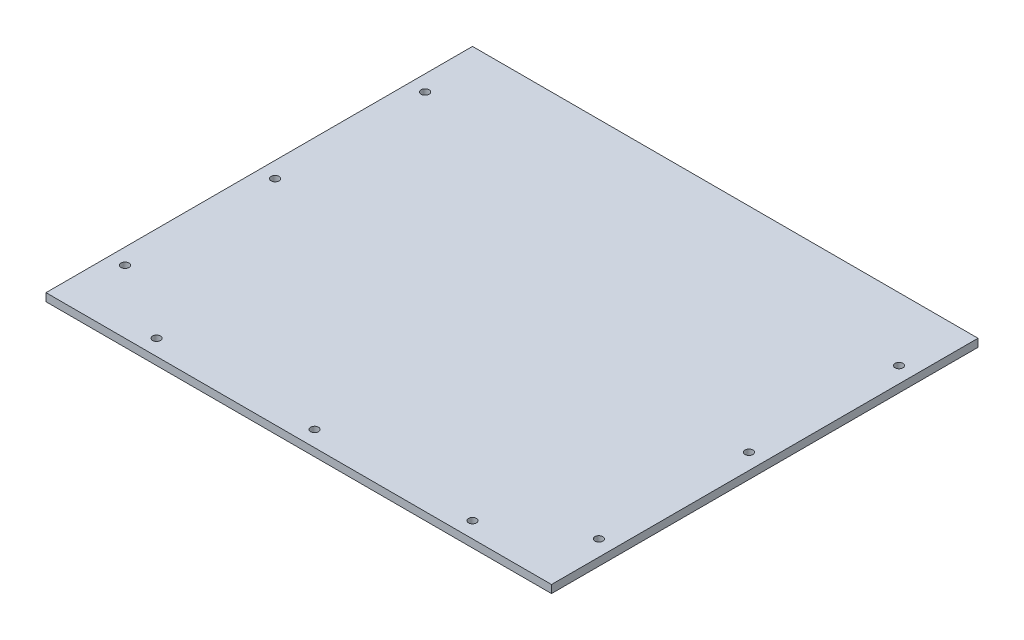
SolidWorks part; units mm, degrees
ref_plane "Front Plane" through (0, 0, 0) normal (0, 0, 1) x (1, 0, 0)
ref_plane "Top Plane" through (0, 0, 0) normal (0, 1, 0) x (1, 0, 0)
ref_plane "Right Plane" through (0, 0, 0) normal (1, 0, 0) x (0, 0, -1)
sketch "Sketch1" plane through (0, 0, 0) normal (0, 1, 0) x (1, 0, 0)
  line L0 (406.4, 0) -> (406.4, 342.9) construction
  line L1 (0, 0) -> (406.4, 0)
  line L2 (0, 0) -> (0, 342.9)
  line L3 (0, 342.9) -> (406.4, 342.9)
  line L4 (406.4, 0) -> (406.4, 342.9)
  line L5 (406.4, 0) -> (406.4, 342.9) construction
  line L6 (387.3669, 342.9) -> (384.1496, 342.9) construction
  line L7 (387.3669, 342.9) -> (384.1496, 342.9) construction
extrude "Boss-Extrude1" add sketch "Sketch1" along normal blind 6.35
sketch "Sketch3" plane through (0, 6.35, 0) normal (0, 1, 0) x (1, 0, 0)
  line L0 (0, 342.9) -> (0, 0) construction
  line L1 (25.4, 25.4) -> (381, 25.4) construction
  line L2 (25.4, 25.4) -> (25.4, 317.5) construction
  line L3 (25.4, 317.5) -> (381, 317.5) construction
  line L4 (381, 25.4) -> (381, 317.5) construction
  line L5 (0, 0) -> (406.4, 0) construction
  line L6 (406.4, 0) -> (406.4, 342.9) construction
  line L7 (406.4, 342.9) -> (0, 342.9) construction
  line L8 (0, 171.45) -> (406.4, 171.45) construction
  line L9 (203.2, 0) -> (203.2, 342.9) construction
  line L10 (12.7, 342.9) -> (12.7, 0) construction
  line L11 (393.7, 342.9) -> (393.7, 0) construction
  line L12 (406.4, 12.7) -> (0, 12.7) construction
  line L13 (12.7, 292.1) -> (393.7, 292.1) construction
  line L14 (12.7, 50.8) -> (393.7, 50.8) construction
  circle A0 centre (203.2, 12.7) radius 3.175
  circle A1 centre (330.2, 12.7) radius 3.175
  circle A2 centre (76.2, 12.7) radius 3.175
  circle A3 centre (12.7, 171.45) radius 3.175
  circle A4 centre (393.7, 171.45) radius 3.175
  circle A5 centre (12.7, 292.1) radius 3.175
  circle A6 centre (12.7, 50.8) radius 3.175
  circle A7 centre (393.7, 50.8) radius 3.175
  circle A8 centre (393.7, 292.1) radius 3.175
  dimension "D8" = 6.35
  dimension "D1" = 25.4
  dimension "D2" = 25.4
  dimension "D3" = 25.4
  dimension "D4" = 25.4
  dimension "D5" = 12.7
  dimension "D6" = 12.7
  dimension "D7" = 12.7
  dimension "D9" = 76.2
  dimension "D10" = 76.2
  dimension "D11" = 50.8
  dimension "D12" = 50.8
extrude "Cut-Extrude1" cut sketch "Sketch3" against normal through all
equation "\"D9@Sketch3\"=3in"
